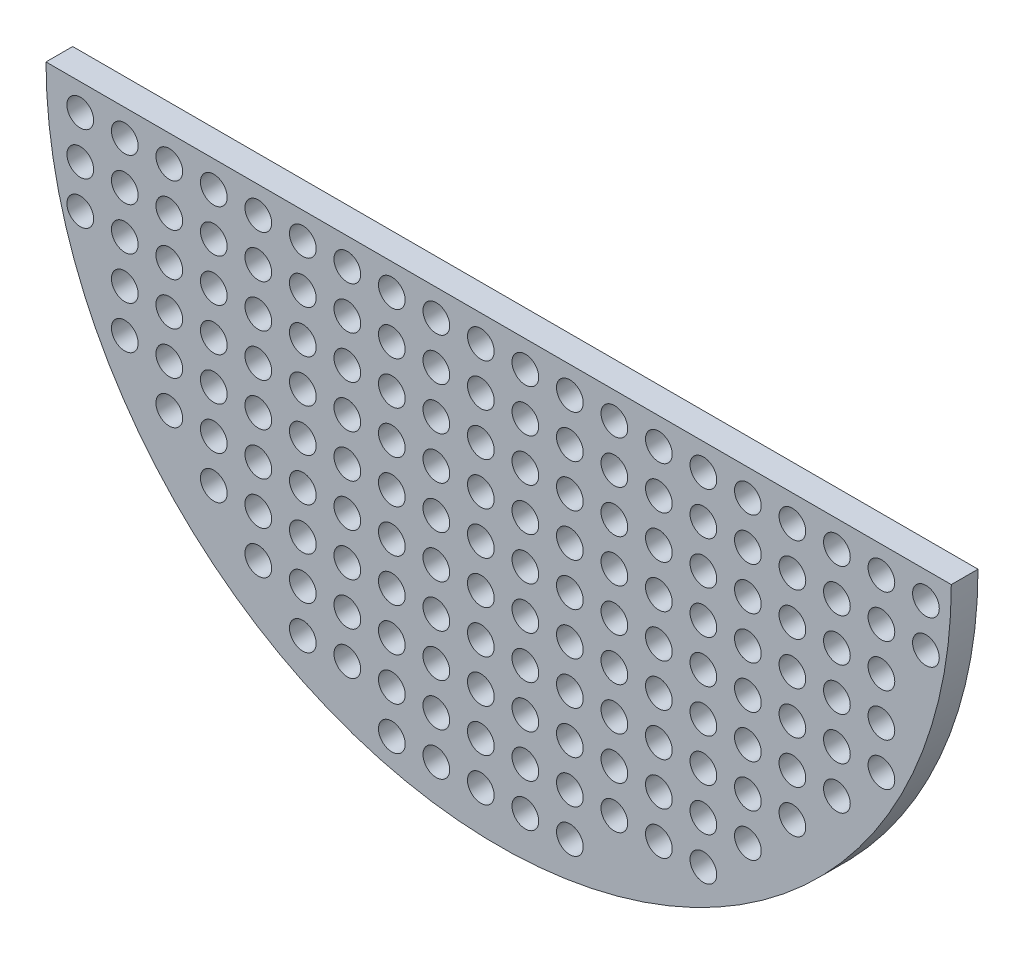
SolidWorks part; units mm, degrees
ref_plane "Front Plane" through (0, 0, 0) normal (0, 0, 1) x (1, 0, 0)
ref_plane "Top Plane" through (0, 0, 0) normal (0, 1, 0) x (1, 0, 0)
ref_plane "Right Plane" through (0, 0, 0) normal (1, 0, 0) x (0, 0, -1)
sketch "Sketch1" plane through (0, 0, 0) normal (0, 0, 1) x (1, 0, 0)
  line L0 (-50.85, 0) -> (50.85, 0)
  arc A0 (-50.85, 0) -> (50.85, 0) centre (0, 0) ccw
  dimension "D1" = 101.7
extrude "Boss-Extrude1" add sketch "Sketch1" along normal mid plane 3
sketch "Sketch2" plane through (0, 0, 1.5) normal (0, 0, 1) x (1, 0, 0)
  line L0 (50.85, 0) -> (-50.85, 0) construction
  circle A0 centre (-47, -3) radius 1.5
  dimension "D2" = 3
  dimension "D1" = 47
  dimension "D3" = 3
extrude "Cut-Extrude1" cut sketch "Sketch2" against normal through all
ref_axis "Axis1" through (0, 2.0425, 0) along (0, -1, 0)
pattern_linear "LPattern1" count 20 spacing 5 along (1, 0, 0) count 10 spacing 4.8 along (0, -1, 0) skipping (0, 3), (0, 4), (0, 5), (0, 6), (0, 7), (0, 8), (0, 9), (1, 5), (1, 6), (1, 7), (1, 8), (1, 9), (2, 6), (2, 7), (2, 8), (2, 9), (3, 7), (3, 8), (3, 9), (4, 8), (4, 9), (5, 9), (6, 9), (12, 9), (13, 9), (14, 9), (15, 8), (15, 9), (16, 7), (16, 8), (16, 9), (17, 6), (17, 7), (17, 8), (17, 9), (18, 5), (18, 6), (18, 7), (18, 8), (18, 9), (19, 2), (19, 3), (19, 4), (19, 5), (19, 6), (19, 7), (19, 8), (19, 9) of "Cut-Extrude1"
